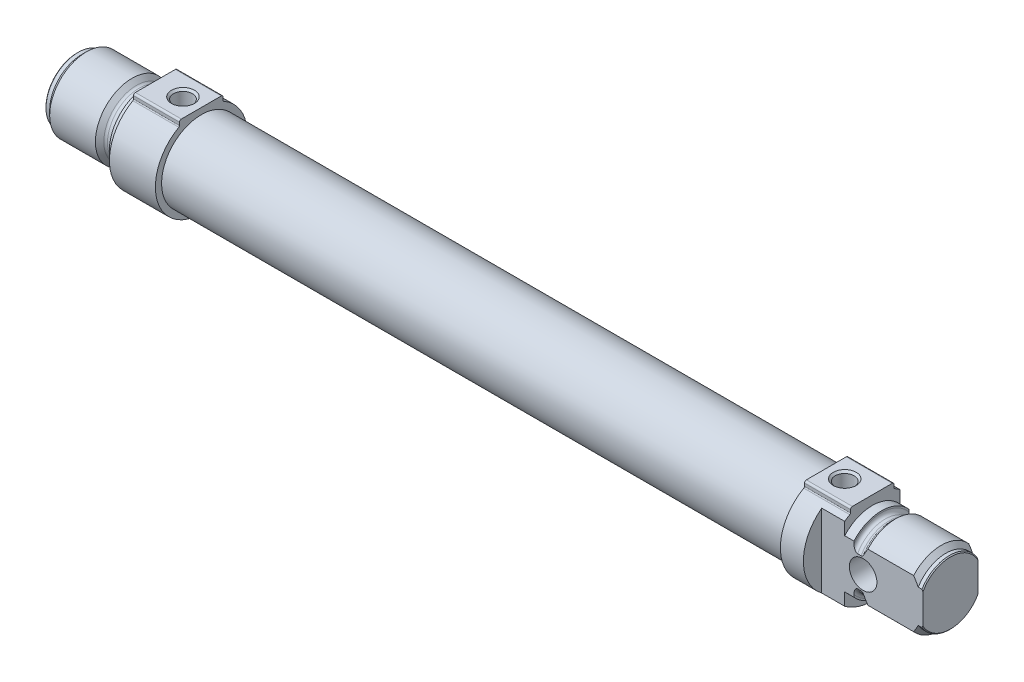
SolidWorks part; units mm, degrees
ref_plane "Front Plane" through (0, 0, 0) normal (0, 0, 1) x (1, 0, 0)
ref_plane "Top Plane" through (0, 0, 0) normal (0, 1, 0) x (1, 0, 0)
ref_plane "Right Plane" through (0, 0, 0) normal (1, 0, 0) x (0, 0, -1)
sketch "Sketch1" plane through (0, 0, 0) normal (0, 0, 1) x (1, 0, 0)
  line L0 (0, 0) -> (0, 6.8)
  line L1 (0, 6.8) -> (0.2, 7)
  line L2 (0.2, 7) -> (1, 7)
  line L3 (1, 7) -> (2, 8)
  line L4 (2, 8) -> (11.95, 8)
  line L5 (11.95, 8) -> (12.8657, 7.0843)
  line L6 (13.4314, 6.85) -> (14.2, 6.85)
  line L7 (15, 7.65) -> (15, 8)
  line L8 (15, 8) -> (17, 8)
  line L9 (17, 8) -> (17, 0)
  line L10 (17, 0) -> (0, 0)
  line L11 (17, 0) -> (0, 0) construction
  arc A0 (12.8657, 7.0843) -> (13.4314, 6.85) centre (13.4314, 7.65) ccw
  arc A1 (14.2, 6.85) -> (15, 7.65) centre (14.2, 7.65) ccw
revolve "Revolve1" add sketch "Sketch1" angle 360 about L11 reverse direction yes
cosmetic thread "Cosmetic Thread1" parameters "D1"=10.87, "D2"=14.16
ref_plane "Plane1" through (21.1, 0, 0) normal (1, 0, 0) x (0, 0, -1)
ref_plane "Plane2" through (9, 0, 0) normal (1, 0, 0) x (0, 0, -1)
ref_plane "Plane3" through (0, -11, 0) normal (0, 1, 0) x (1, 0, 0)
ref_plane "Plane4" through (0, 11, 0) normal (0, 1, 0) x (1, 0, 0)
ref_plane "Plane5" through (0, 0, 0) normal (0, 1, 0) x (1, 0, 0)
ref_plane "Plane6" through (0, 0, 0) normal (0, 1, 0) x (1, 0, 0)
ref_plane "Plane7" through (17, 0, 0) normal (1, 0, 0) x (0, 0, -1)
ref_plane "Plane8" through (17, 0, 0) normal (1, 0, 0) x (0, 0, -1)
ref_plane "Plane9" through (27, 0, 0) normal (1, 0, 0) x (0, 0, -1)
ref_plane "Plane10" through (17, 0, 0) normal (1, 0, 0) x (0, 0, -1)
ref_plane "Plane11" through (17, 0, 0) normal (1, 0, 0) x (0, 0, -1)
sketch "Sketch2" plane through (17, 0, 0) normal (1, 0, 0) x (0, 0, -1)
  line L0 (4.75, 8.9771) -> (4.75, 9.6)
  line L1 (4.35, 10) -> (-4.35, 10)
  line L2 (-4.75, 9.6) -> (-4.75, 8.9771)
  arc A0 (-4.9029, 8.7156) -> (4.9029, 8.7156) centre (0, 0) ccw
  arc A1 (4.9029, 8.7156) -> (4.75, 8.9771) centre (5.05, 8.9771) cw
  arc A2 (4.75, 9.6) -> (4.35, 10) centre (4.35, 9.6) ccw
  arc A3 (-4.35, 10) -> (-4.75, 9.6) centre (-4.35, 9.6) ccw
  arc A4 (-4.75, 8.9771) -> (-4.9029, 8.7156) centre (-5.05, 8.9771) cw
extrude "Boss-Extrude1" add sketch "Sketch2" along normal blind 10
ref_plane "Plane12" through (23, 0, 0) normal (1, 0, 0) x (0, 0, -1)
ref_plane "Plane13" through (0, 0, 0) normal (0, 0, 1) x (1, 0, 0)
ref_plane "Plane14" through (0, 0, -6.5) normal (0, 0, 1) x (1, 0, 0)
ref_plane "Plane15" through (0, 0, 0) normal (0, 1, 0) x (1, 0, 0)
ref_plane "Plane16" through (0, 5.5, 0) normal (0, 1, 0) x (1, 0, 0)
ref_plane "Plane17" through (0, 0, -6.6) normal (0, 0, 1) x (1, 0, 0)
ref_plane "Plane18" through (0, 0, 0) normal (0, 1, 0) x (1, 0, 0)
ref_plane "Plane19" through (0, 5.5, 0) normal (0, 1, 0) x (1, 0, 0)
ref_plane "Plane20" through (0, 6.4628, -1.1396) normal (0, 0.9848, -0.1736) x (1, 0, 0)
ref_plane "Plane21" through (0, 4.9856, -0.8791) normal (0, 0.9848, -0.1736) x (1, 0, 0)
sketch "Sketch3" plane through (0, 0, 0) normal (0, 0, 1) x (1, 0, 0)
  line L0 (27, 0) -> (27, 8.65)
  line L1 (27, 8.65) -> (163, 8.65)
  line L2 (163, 8.65) -> (163, 0)
  line L3 (163, 0) -> (27, 0)
  line L4 (163, 0) -> (27, 0) construction
revolve "Revolve2" add sketch "Sketch3" angle 360 about L4 reverse direction yes
ref_plane "Plane22" through (163, 0, 0) normal (1, 0, 0) x (0, 0, -1)
sketch "Sketch4" plane through (163, 0, 0) normal (1, 0, 0) x (0, 0, -1)
  line L0 (4.75, 8.9771) -> (4.75, 9.6)
  line L1 (4.35, 10) -> (-4.35, 10)
  line L2 (-4.75, 9.6) -> (-4.75, 8.9771)
  arc A0 (-4.9029, 8.7156) -> (4.9029, 8.7156) centre (0, 0) ccw
  arc A1 (4.9029, 8.7156) -> (4.75, 8.9771) centre (5.05, 8.9771) cw
  arc A2 (4.75, 9.6) -> (4.35, 10) centre (4.35, 9.6) ccw
  arc A3 (-4.35, 10) -> (-4.75, 9.6) centre (-4.35, 9.6) ccw
  arc A4 (-4.75, 8.9771) -> (-4.9029, 8.7156) centre (-5.05, 8.9771) cw
extrude "Boss-Extrude2" add sketch "Sketch4" along normal blind 10
ref_plane "Plane23" through (165.35, 0, 0) normal (1, 0, 0) x (0, 0, -1)
ref_plane "Plane24" through (167, 0, 0) normal (1, 0, 0) x (0, 0, -1)
ref_plane "Plane25" through (0, 0, 6.6) normal (0, 0, 1) x (1, 0, 0)
ref_plane "Plane26" through (0, 0, 0) normal (0, 1, 0) x (1, 0, 0)
ref_plane "Plane27" through (0, 5.5, 0) normal (0, 1, 0) x (1, 0, 0)
ref_plane "Plane28" through (0, 6.4628, 1.1396) normal (0, 0.9848, 0.1736) x (1, 0, 0)
ref_plane "Plane29" through (0, 4.9856, 0.8791) normal (0, 0.9848, 0.1736) x (1, 0, 0)
ref_plane "Plane30" through (211, 0, 0) normal (1, 0, 0) x (0, 0, -1)
sketch "Sketch5" plane through (0, 0, 0) normal (0, 0, 1) x (1, 0, 0)
  line L0 (173, 0) -> (173, 8)
  line L1 (173, 8) -> (175, 8)
  line L2 (175, 8) -> (175, 7.65)
  line L3 (175.8, 6.85) -> (176.5686, 6.85)
  line L4 (177.1343, 7.0843) -> (178.05, 8)
  line L5 (178.05, 8) -> (188, 8)
  line L6 (188, 8) -> (189, 7)
  line L7 (189, 7) -> (189.8, 7)
  line L8 (189.8, 7) -> (190, 6.8)
  line L9 (190, 6.8) -> (190, 0)
  line L10 (190, 0) -> (173, 0)
  line L11 (190, 0) -> (173, 0) construction
  arc A0 (175, 7.65) -> (175.8, 6.85) centre (175.8, 7.65) ccw
  arc A1 (176.5686, 6.85) -> (177.1343, 7.0843) centre (176.5686, 7.65) ccw
revolve "Revolve3" add sketch "Sketch5" angle 360 about L11 reverse direction yes
cosmetic thread "Cosmetic Thread2" parameters "D1"=9.87, "D2"=14.16
ref_plane "Plane31" through (201, 0, 0) normal (1, 0, 0) x (0, 0, -1)
ref_plane "Plane32" through (211, 0, 0) normal (1, 0, 0) x (0, 0, -1)
ref_plane "Plane33" through (211, 0, 0) normal (1, 0, 0) x (0, 0, -1)
sketch "Sketch6" plane through (0, 0, 0) normal (0, 1, 0) x (1, 0, 0)
  line L0 (168, 18) -> (168, 6)
  line L1 (168, 6) -> (190, 6)
  line L2 (190, 6) -> (190, -6)
  line L3 (190, -6) -> (168, -6)
  line L4 (168, -6) -> (168, -18)
  line L5 (168, -18) -> (202, -18)
  line L6 (202, -18) -> (202, 18)
  line L7 (202, 18) -> (168, 18)
extrude "Cut-Extrude1" cut sketch "Sketch6" along normal blind 10 and the other way blind 10
ref_plane "Plane34" through (177, 0, 0) normal (1, 0, 0) x (0, 0, -1)
sketch "Sketch7" plane through (177, 0, 0) normal (1, 0, 0) x (0, 0, -1)
  line L0 (-6, 0) -> (-6, 3)
  line L1 (-6, 3) -> (6, 3)
  line L2 (6, 3) -> (6, 0)
  line L3 (6, 0) -> (-6, 0)
  line L4 (6, 0) -> (-6, 0) construction
revolve "Cut-Revolve1" cut sketch "Sketch7" angle 360 about L4 reverse direction yes
hole_wizard "Hole1" positions "Sketch9" profile "Sketch8" legacy
sketch "Sketch9" plane through (0, 10, 0) normal (0, 1, 0) x (1, 0, 0)
  point P0 (23, 0)
sketch "Sketch8" plane through (23, 10, 0) normal (1, 0, 0) x (0, 0, 1)
  line L0 (0, 0) -> (0, 10)
  line L1 (0, 10) -> (2.067, 10)
  line L2 (2.067, 10) -> (2.067, 0.433)
  line L3 (2.067, 0.433) -> (2.5, 0)
  line L4 (2.5, 0) -> (0, 0)
  line L5 (0, -6.4453) -> (0, 115.525) construction
  line L6 (-2.067, 0.433) -> (-2.5, 0) construction
  dimension "Diameter" = 4.134
  dimension "Depth" = 10
  dimension "C-Sink Angle" = 90
  dimension "C-Sink Diameter" = 5
cosmetic thread "Cosmetic Thread3" parameters "D1"=7, "D2"=5
hole_wizard "Hole2" positions "Sketch11" profile "Sketch10" legacy
sketch "Sketch11" plane through (0, 10, 0) normal (0, 1, 0) x (1, 0, 0)
  point P0 (167, 0)
sketch "Sketch10" plane through (167, 10, 0) normal (1, 0, 0) x (0, 0, 1)
  line L0 (0, 0) -> (0, 12.1934)
  line L1 (0, 12.1934) -> (2.067, 11)
  line L2 (2.067, 11) -> (2.067, 0.433)
  line L3 (2.067, 0.433) -> (2.5, 0)
  line L4 (2.5, 0) -> (0, 0)
  line L5 (0, -14.3089) -> (0, 102.4216) construction
  line L6 (0, 12.1934) -> (-2.067, 11) construction
  line L7 (-2.067, 0.433) -> (-2.5, 0) construction
  dimension "Diameter" = 4.134
  dimension "Depth" = 11
  dimension "C-Sink Diameter" = 5
  dimension "C-Sink Angle" = 90
  dimension "Drill Angle" = 120
cosmetic thread "Cosmetic Thread4" parameters "D1"=6, "D2"=5
sketch "Sketch12" plane through (0, 0, 0) normal (0, 0, 1) x (1, 0, 0)
  line L0 (-5, 0) -> (-5, 3)
  line L1 (-5, 3) -> (41.2, 3)
  line L2 (41.2, 3) -> (41.2, 8)
  line L3 (41.2, 8) -> (145.2, 8)
  line L4 (145.2, 8) -> (145.2, 0)
  line L5 (145.2, 0) -> (-5, 0)
  line L6 (145.2, 0) -> (-5, 0) construction
revolve "Cut-Revolve2" cut sketch "Sketch12" angle 360 about L6 reverse direction yes
ref_plane "Plane35" through (-5, 0, 0) normal (1, 0, 0) x (0, 0, -1)
ref_plane "Plane36" through (0, 10, 0) normal (0, 1, 0) x (1, 0, 0)
ref_plane "Plane37" through (7, 0, 0) normal (1, 0, 0) x (0, 0, -1)
ref_plane "Plane38" through (0, 0, 0) normal (1, 0, 0) x (0, 0, -1)
ref_plane "Plane39" through (17, 0, 0) normal (1, 0, 0) x (0, 0, -1)
ref_plane "Plane40" through (173, 0, 0) normal (1, 0, 0) x (0, 0, -1)
ref_plane "Plane41" through (17, 0, 0) normal (1, 0, 0) x (0, 0, -1)
ref_plane "Plane42" through (0, 10, 0) normal (0, 1, 0) x (1, 0, 0)
ref_plane "Plane43" through (36.5, 0, 0) normal (1, 0, 0) x (0, 0, -1)
ref_plane "Plane44" through (153.5, 0, 0) normal (1, 0, 0) x (0, 0, -1)
ref_plane "Plane45" through (0, 0, 0) normal (0, 0, 1) x (1, 0, 0)
ref_plane "Plane46" through (17, 0, 0) normal (1, 0, 0) x (0, 0, -1)
ref_plane "Plane47" through (0, 10, 0) normal (0, 1, 0) x (1, 0, 0)
ref_plane "FDT_FRONT XY" through (17, 0, 0) normal (1, 0, 0) x (0, 0, -1)
ref_plane "FDT_FRONT XZ" through (0, 0, 0) normal (0, -1, 0) x (-1, 0, 0)
ref_plane "FDT_FRONT YZ" through (0, 0, 0) normal (0, 0, -1) x (-1, 0, 0)
ref_axis "FDT_FRONT X" through (17, 0, 80.9) along (0, 0, -1)
ref_axis "FDT_FRONT Y" through (17, -50, 0) along (0, 1, 0)
ref_axis "FDT_FRONT Z" through (80.9, 0, 0) along (-1, 0, 0)
sketch3d "FDT_FRONT"
  point P0 (17, 0, 0)
ref_plane "FDT_QSFRONT XY" through (0, 10, 0) normal (0, 1, 0) x (1, 0, 0)
ref_plane "FDT_QSFRONT XZ" through (23, 0, 0) normal (-1, 0, 0) x (0, 0, 1)
ref_plane "FDT_QSFRONT YZ" through (0, 0, 0) normal (0, 0, 1) x (1, 0, 0)
ref_axis "FDT_QSFRONT X" through (23, 10, -50) along (0, 0, 1)
ref_axis "FDT_QSFRONT Y" through (-80.9, 10, 0) along (1, 0, 0)
ref_axis "FDT_QSFRONT Z" through (23, 50, 0) along (0, -1, 0)
sketch3d "FDT_QSFRONT"
  point P0 (23, 10, 0)
ref_plane "FDT_QSREAR XY" through (0, 10, 0) normal (0, 1, 0) x (1, 0, 0)
ref_plane "FDT_QSREAR XZ" through (167, 0, 0) normal (-1, 0, 0) x (0, 0, 1)
ref_plane "FDT_QSREAR YZ" through (0, 0, 0) normal (0, 0, 1) x (1, 0, 0)
ref_axis "FDT_QSREAR X" through (167, 10, -50) along (0, 0, 1)
ref_axis "FDT_QSREAR Y" through (-80.9, 10, 0) along (1, 0, 0)
ref_axis "FDT_QSREAR Z" through (167, 50, 0) along (0, -1, 0)
sketch3d "FDT_QSREAR"
  point P0 (167, 10, 0)
ref_plane "FDT_REAR XY" through (173, 0, 0) normal (-1, 0, 0) x (0, 0, 1)
ref_plane "FDT_REAR XZ" through (0, 0, 0) normal (0, 1, 0) x (1, 0, 0)
ref_plane "FDT_REAR YZ" through (0, 0, 0) normal (0, 0, -1) x (-1, 0, 0)
ref_axis "FDT_REAR X" through (173, 0, 80.9) along (0, 0, -1)
ref_axis "FDT_REAR Y" through (173, 50, 0) along (0, -1, 0)
ref_axis "FDT_REAR Z" through (-80.9, 0, 0) along (1, 0, 0)
sketch3d "FDT_REAR"
  point P0 (173, 0, 0)
ref_plane "FDT_SMBR1 XY" through (36.5, 0, 0) normal (-1, 0, 0) x (0, 0, 1)
ref_plane "FDT_SMBR1 XZ" through (0, 0, 0) normal (0, -1, 0) x (-1, 0, 0)
ref_plane "FDT_SMBR1 YZ" through (0, 0, 0) normal (0, 0, 1) x (1, 0, 0)
ref_axis "FDT_SMBR1 X" through (36.5, 0, -80.9) along (0, 0, 1)
ref_axis "FDT_SMBR1 Y" through (36.5, -50, 0) along (0, 1, 0)
ref_axis "FDT_SMBR1 Z" through (-80.9, 0, 0) along (1, 0, 0)
sketch3d "FDT_SMBR1"
  point P0 (36.5, 0, 0)
ref_plane "FDT_SMBR2 XY" through (153.5, 0, 0) normal (-1, 0, 0) x (0, 0, 1)
ref_plane "FDT_SMBR2 XZ" through (0, 0, 0) normal (0, -1, 0) x (-1, 0, 0)
ref_plane "FDT_SMBR2 YZ" through (0, 0, 0) normal (0, 0, 1) x (1, 0, 0)
ref_axis "FDT_SMBR2 X" through (153.5, 0, -80.9) along (0, 0, 1)
ref_axis "FDT_SMBR2 Y" through (153.5, -50, 0) along (0, 1, 0)
ref_axis "FDT_SMBR2 Z" through (-80.9, 0, 0) along (1, 0, 0)
sketch3d "FDT_SMBR2"
  point P0 (153.5, 0, 0)
ref_plane "FDT_SWIVELAXIS XY" through (0, 0, 0) normal (0, 0, 1) x (1, 0, 0)
ref_plane "FDT_SWIVELAXIS XZ" through (0, 0, 0) normal (0, -1, 0) x (-1, 0, 0)
ref_plane "FDT_SWIVELAXIS YZ" through (177, 0, 0) normal (1, 0, 0) x (0, 0, -1)
ref_axis "FDT_SWIVELAXIS X" through (-80.9, 0, 0) along (1, 0, 0)
ref_axis "FDT_SWIVELAXIS Y" through (177, -50, 0) along (0, 1, 0)
ref_axis "FDT_SWIVELAXIS Z" through (177, 0, 80.9) along (0, 0, -1)
sketch3d "FDT_SWIVELAXIS"
  point P0 (177, 0, 0)
ref_plane "NUT XY" through (7, 0, 0) normal (1, 0, 0) x (0, 0, -1)
ref_plane "NUT XZ" through (0, 0, 0) normal (0, -1, 0) x (-1, 0, 0)
ref_plane "NUT YZ" through (0, 0, 0) normal (0, 0, -1) x (-1, 0, 0)
ref_axis "NUT X" through (7, 0, 80.9) along (0, 0, -1)
ref_axis "NUT Y" through (7, -50, 0) along (0, 1, 0)
ref_axis "NUT Z" through (80.9, 0, 0) along (-1, 0, 0)
sketch3d "NUT"
  point P0 (7, 0, 0)
ref_plane "ZR XY" through (0, 0, 0) normal (1, 0, 0) x (0, 0, -1)
ref_plane "ZR XZ" through (0, 0, 0) normal (0, -1, 0) x (-1, 0, 0)
ref_plane "ZR YZ" through (0, 0, 0) normal (0, 0, -1) x (-1, 0, 0)
ref_axis "ZR X" through (0, 0, 80.9) along (0, 0, -1)
ref_axis "ZR Y" through (0, -50, 0) along (0, 1, 0)
ref_axis "ZR Z" through (80.9, 0, 0) along (-1, 0, 0)
sketch3d "ZR"
  point P0 (0, 0, 0)
ref_plane "ZYL XY" through (17, 0, 0) normal (1, 0, 0) x (0, 0, -1)
ref_plane "ZYL XZ" through (0, 0, 0) normal (0, -1, 0) x (-1, 0, 0)
ref_plane "ZYL YZ" through (0, 0, 0) normal (0, 0, -1) x (-1, 0, 0)
ref_axis "ZYL X" through (17, 0, 80.9) along (0, 0, -1)
ref_axis "ZYL Y" through (17, -50, 0) along (0, 1, 0)
ref_axis "ZYL Z" through (80.9, 0, 0) along (-1, 0, 0)
sketch3d "ZYL"
  point P0 (17, 0, 0)
other "Freeze***"
